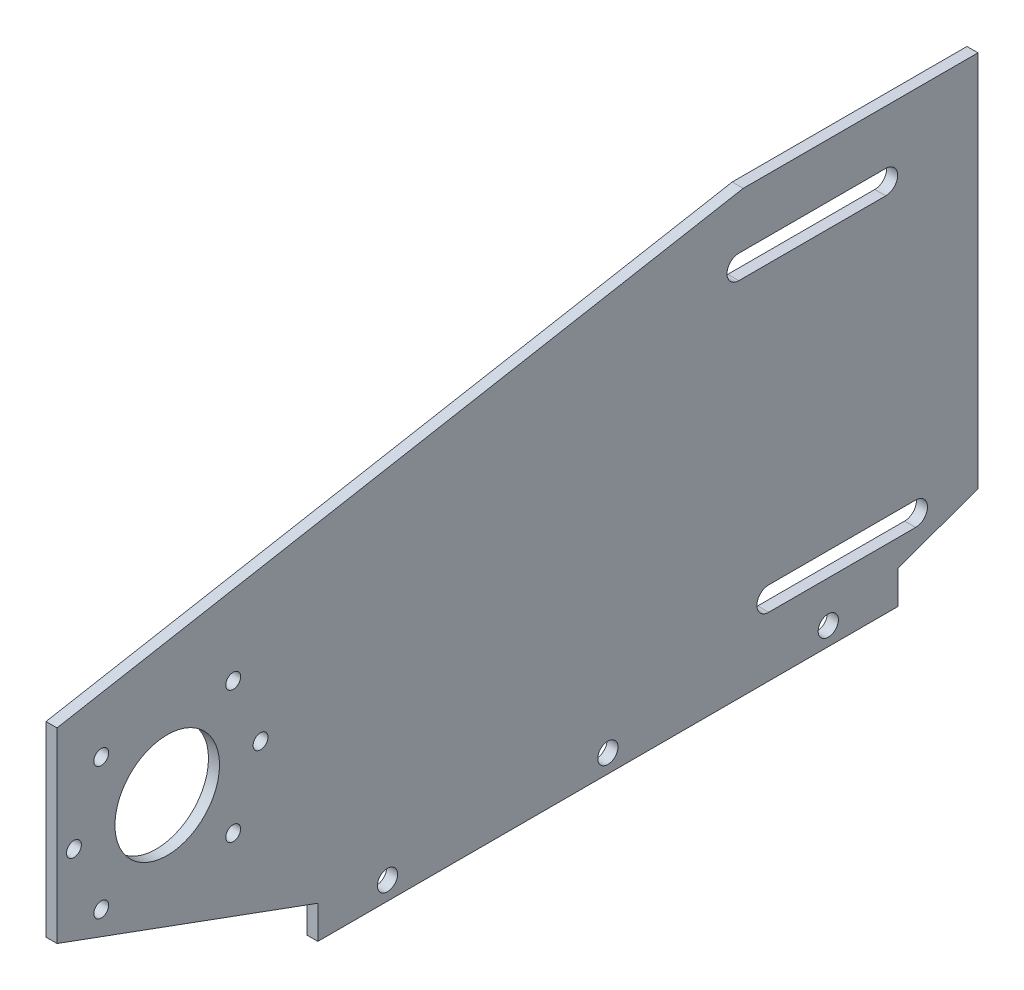
SolidWorks part; units mm, degrees
ref_plane "Front Plane" through (0, 0, 0) normal (0, 0, 1) x (1, 0, 0)
ref_plane "Top Plane" through (0, 0, 0) normal (0, 1, 0) x (1, 0, 0)
ref_plane "Right Plane" through (0, 0, 0) normal (1, 0, 0) x (0, 0, -1)
sketch "Sketch1" plane through (0, 0, 0) normal (1, 0, 0) x (0, 0, -1)
  line L1 (0, 0) -> (300, 0)
  line L2 (0, 0) -> (0, 150)
  line L3 (0, 150) -> (300, 150)
  line L4 (300, 0) -> (300, 150)
  circle A0 centre (30, 55) radius 14.235
  dimension "D1" = 300
  dimension "D5" = 28.47
  dimension "D4" = 55
  dimension "D2" = 150
  dimension "D3" = 30
extrude "Boss-Extrude1" add sketch "Sketch1" along normal blind 3
sketch "Sketch2" plane through (0, 0, 0) normal (-1, 0, 0) x (0, 0, 1)
  line L0 (-225.6114, 104.9384) -> (-185.6114, 104.9384) construction
  line L3 (-185.6114, 98.4784) -> (-225.6114, 98.4784) construction
  line L6 (-193.7436, 16.2317) -> (-233.7436, 16.2317) construction
  line L11 (-233.7436, 22.6817) -> (-193.7436, 22.6817) construction
  line L14 (0, 0) -> (-300, 0) construction
  line L17 (0, 150) -> (0, 0) construction
  line L18 (-225.6114, 104.9384) -> (-185.6114, 104.9384)
  line L19 (-185.6114, 98.4784) -> (-225.6114, 98.4784)
  line L20 (-193.7436, 16.2317) -> (-233.7436, 16.2317)
  line L21 (-233.7436, 22.6817) -> (-193.7436, 22.6817)
  arc A2 (-225.6114, 104.9384) -> (-225.6114, 98.4784) centre (-225.6114, 101.7084) ccw construction
  circle A12 centre (-10, 110) radius 3.225
  arc A14 (-185.6114, 98.4784) -> (-185.6114, 104.9384) centre (-185.6114, 101.7084) ccw construction
  arc A15 (-193.7436, 16.2317) -> (-193.7436, 22.6817) centre (-193.7436, 19.4567) ccw construction
  arc A16 (-233.7436, 22.6817) -> (-233.7436, 16.2317) centre (-233.7436, 19.4567) ccw construction
  arc A17 (-225.6114, 104.9384) -> (-225.6114, 98.4784) centre (-225.6114, 101.7084) ccw
  arc A18 (-185.6114, 98.4784) -> (-185.6114, 104.9384) centre (-185.6114, 101.7084) ccw
  arc A19 (-193.7436, 16.2317) -> (-193.7436, 22.6817) centre (-193.7436, 19.4567) ccw
  arc A20 (-233.7436, 22.6817) -> (-233.7436, 16.2317) centre (-233.7436, 19.4567) ccw
  dimension "D14" = 6.45
  dimension "D20" = 10
  dimension "D21" = 110
extrude "Cut-Extrude1" cut sketch "Sketch2" against normal up to next
sketch "Sketch4" plane through (3, 0, 0) normal (1, 0, 0) x (0, 0, -1)
  line L4 (0, 150) -> (0, 0)
  line L5 (0, 0) -> (300, 0)
  line L6 (300, 0) -> (300, 150)
  line L7 (300, 150) -> (0, 150)
  line L8 (0, 150) -> (0, 0)
  line L9 (0, 0) -> (300, 0)
  line L10 (300, 0) -> (300, 150)
  line L11 (300, 150) -> (0, 150)
  circle A0 centre (47.9605, 37.0395) radius 2.0193 construction
  circle A1 centre (47.9605, 37.0395) radius 2.0193
  circle A2 centre (47.9605, 72.9605) radius 2.0193 construction
  circle A3 centre (47.9605, 72.9605) radius 2.0193
  circle A4 centre (55.4, 55) radius 2.0193 construction
  circle A5 centre (55.4, 55) radius 2.0193
  circle A6 centre (12.0395, 72.9605) radius 2.0193 construction
  circle A7 centre (12.0395, 72.9605) radius 2.0193
  circle A8 centre (4.6, 55) radius 2.0193 construction
  circle A9 centre (4.6, 55) radius 2.0193
  circle A10 centre (12.0395, 37.0395) radius 2.0193 construction
  circle A11 centre (12.0395, 37.0395) radius 2.0193
  dimension "D1" = 0
extrude "Cut-Extrude4" cut sketch "Sketch4" against normal through all contours A11 | A7 | A9 | A1 | A5 | A3 region at (3, 37.0395, -12.0395)
sketch "Sketch5" plane through (0, 0, 0) normal (-1, 0, 0) x (0, 0, 1)
  line L7 (-71, 0) -> (-71, 9) construction
  line L8 (-71, 9) -> (0, 35) construction
  line L9 (-71, 0) -> (-71, 9)
  line L10 (-71, 9) -> (0, 35)
  line L11 (0, 35) -> (0, 0)
  line L12 (0, 0) -> (-71, 0)
  line L13 (0, 85.8486) -> (-186.8026, 119.6415) construction
  line L14 (0, 85.8486) -> (-186.8026, 119.6415)
  line L16 (-300, 150) -> (0, 150) construction
  line L17 (0, 150) -> (0, 85.8486)
  line L19 (-300.3105, 150) -> (0, 150)
  line L20 (-186.8026, 119.6415) -> (-250.718, 119.6415) construction
  line L21 (-186.8026, 119.6415) -> (-300.3105, 119.6415)
  line L22 (-300.3105, 119.6415) -> (-300.3105, 150)
extrude "Cut-Extrude5" cut sketch "Sketch5" against normal through all
sketch "Sketch6" plane through (0, 0, 0) normal (-1, 0, 0) x (0, 0, 1)
  line L8 (-250.718, 119.6415) -> (-250.718, 16.8759) construction
  line L9 (-228.924, 9) -> (-228.924, 0) construction
  line L10 (-250.718, 16.8759) -> (-228.924, 9) construction
  line L11 (-250.718, 165.7129) -> (-250.718, 16.8759)
  line L12 (-228.924, 9) -> (-228.924, 0)
  line L13 (-250.718, 16.8759) -> (-228.924, 9)
  line L14 (-250.718, 165.7129) -> (-364.8309, 165.7129)
  line L15 (-364.8309, 165.7129) -> (-355.7689, 0)
  line L16 (-355.7689, 0) -> (-228.924, 0)
  line M6 (-300, 119.6415) -> (-300, 0)
  line M7 (-300, 0) -> (-71, 0)
extrude "Cut-Extrude6" cut sketch "Sketch6" against normal blind 10 contours L11 M7 M6 region at (0, 82.816, -304.5522)
sketch "Sketch7" plane through (3, 0, 0) normal (1, 0, 0) x (0, 0, -1)
  line L1 (71, 0) -> (228.924, 0) construction
  circle A0 centre (89.962, 5) radius 2.75
  circle A1 centre (149.962, 5) radius 2.75
  circle A2 centre (209.962, 5) radius 2.75
  point P9 (149.962, 0)
  dimension "D1" = 5.5
  dimension "D2" = 5.5
  dimension "D3" = 5.5
  dimension "D4" = 60
  dimension "D5" = 60
  dimension "D6" = 5
extrude "Cut-Extrude7" cut sketch "Sketch7" against normal through all
